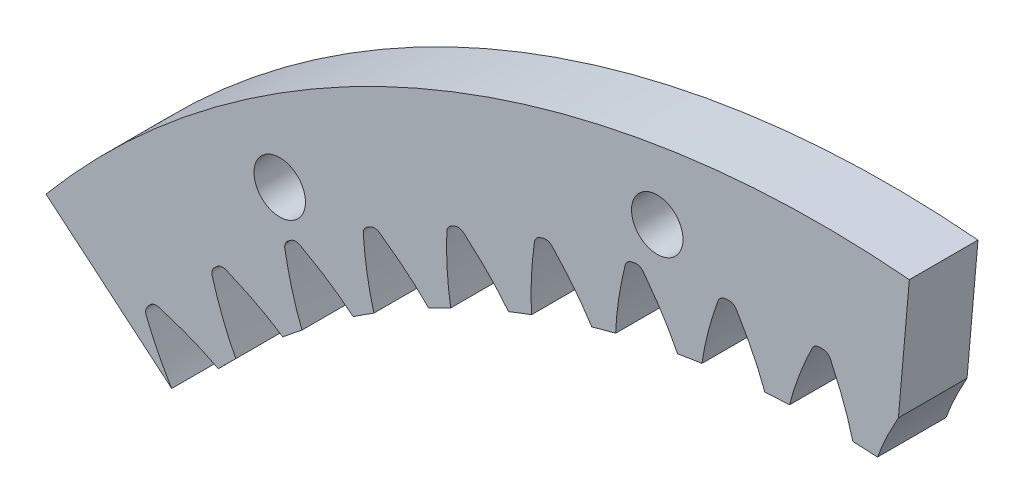
SolidWorks part; units mm, degrees
material "Д16 ГОСТ 4784-97"
ref_plane "FRONT" through (0, 0, 0) normal (0, 0, 1) x (1, 0, 0)
ref_plane "TOP" through (0, 0, 0) normal (0, 1, 0) x (1, 0, 0)
ref_plane "RIGHT" through (0, 0, 0) normal (1, 0, 0) x (0, 0, -1)
ref_axis "Ось1" through (0, 0, 50) along (0, 0, -1)
sketch "SketchRevolveSpurAssembly01Gear" plane through (0, 0, 0) normal (1, 0, 0) x (0, 0, -1)
  line L0 (0, 0) -> (1, 0) construction
  line L1 (-3.525, 48.9583) -> (-3.525, 58.9583)
  line L2 (-3.525, 58.9583) -> (0.475, 58.9583)
  line L3 (0.475, 58.9583) -> (0.475, 48.9583)
  line L4 (0.475, 48.9583) -> (-3.525, 48.9583)
  dimension "MinorDiameter" = 48.9583
  dimension "D1" = 4
  dimension "D2" = 10
revolve "SpurAssembly01Gear" add sketch "SketchRevolveSpurAssembly01Gear" angle 360 about L0
sketch "SketchToothSpurAssembly01Gear" plane through (0, 0, 0) normal (0, 0, 1) x (1, 0, 0)
  arc A0 (48.5511, -1.932) -> (48.5511, 1.932) centre (0, 0) ccw
  spline S0 degree 3 poles (48.5511, 1.932) (48.7541, 1.887) (49.0692, 1.8089) (49.5016, 1.6863) (49.8599, 1.5757) (50.2394, 1.4489) (50.6395, 1.3049) (51.0596, 1.1423) (51.4996, 0.9614) (51.9565, 0.7563) (52.2921, 0.6097) (52.4882, 0.5038) (52.5438, 0.4598) (52.5926, 0.4095) (52.6338, 0.3527) (52.6666, 0.2908) (52.6986, 0.2036) (52.7092, 0.1191) (52.7082, 0.0439) (52.7084, 0) (52.7082, -0.0439) (52.7092, -0.1191) (52.6986, -0.2036) (52.6666, -0.2908) (52.6338, -0.3527) (52.5926, -0.4095) (52.5438, -0.4598) (52.4882, -0.5038) (52.2921, -0.6097) (51.9565, -0.7563) (51.4996, -0.9614) (51.0596, -1.1423) (50.6395, -1.3049) (50.2394, -1.4489) (49.8599, -1.5757) (49.5016, -1.6863) (49.0692, -1.8089) (48.7541, -1.887) (48.5511, -1.932) knots 0 0 0 0 0.065344 0.101973 0.14124 0.183144 0.227687 0.274868 0.324687 0.377144 0.432239 0.439737 0.447061 0.454385 0.461709 0.469032 0.476356 0.490795 0.495397 0.5 0.504603 0.509205 0.523644 0.530968 0.538291 0.545615 0.552939 0.560263 0.567761 0.622856 0.675313 0.725132 0.772313 0.816856 0.85876 0.898027 0.934656 1 1 1 1
extrude "ToothExtrudeCutSpurAssembly01Gear" cut sketch "SketchToothSpurAssembly01Gear" against normal blind 9.525 and the other way blind 9.525
pattern_circular "PatternSpurAssembly01Gear" count 60 every 6 about axis through (0, 0, 50) along (0, 0, -1) of "ToothExtrudeCutSpurAssembly01Gear"
sketch "Эскиз1" plane through (0, 0, 3.525) normal (0, 0, 1) x (1, 0, 0)
  line L0 (0, 0) -> (0, 93.1293) construction
  line L1 (0, 0) -> (-68.1498, 68.1498) construction
  line L2 (0, 0) -> (6.9724, 79.6954)
  line L3 (0, 0) -> (-61.2834, 51.4229)
  line L4 (-9.5506, 54.1644) -> (0, 0) construction
  line L5 (0, 0) -> (-30.0761, 72.6102) construction
  arc A0 (6.9724, 79.6954) -> (-61.2834, 51.4229) centre (0, 0) cw
  circle A1 centre (0, 0) radius 55 construction
  circle A2 centre (-9.5506, 54.1644) radius 1.5
  circle A3 centre (-31.5467, 45.0534) radius 1.5
  dimension "D2" = 5
  dimension "D4" = 79.9999
  dimension "D5" = 110
  dimension "D6" = 3
  dimension "D1" = 45
  dimension "D3" = 5
  dimension "D7" = 10
  dimension "D8" = 22.5
extrude "Вырез-Вытянуть1" cut sketch "Эскиз1" against normal through all
sketch "AuxiliarySketchSpurAssembly01Gear" plane through (0, 0, 0) normal (0, 0, 1) x (1, 0, 0)
  circle A0 centre (0, 0) radius 50 construction
  circle A1 centre (0, 0) radius 46.9846 construction
  circle A2 centre (0, 0) radius 52.7083 construction
  circle A3 centre (0, 0) radius 48.9583 construction
  dimension "PitchDiameter" = 100
  dimension "BaseDiameter" = 93.9693
  dimension "MajorDiameter" = 105.4167
  dimension "MinorDiameter" = 97.9167
